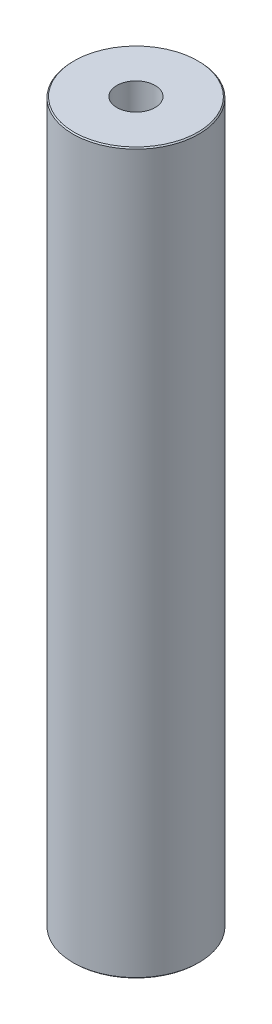
SolidWorks part; units mm, degrees
ref_plane "Front Plane" through (0, 0, 0) normal (0, 0, 1) x (1, 0, 0)
ref_plane "Top Plane" through (0, 0, 0) normal (0, 1, 0) x (1, 0, 0)
ref_plane "Right Plane" through (0, 0, 0) normal (1, 0, 0) x (0, 0, -1)
sketch "Sketch1" plane through (0, 0, 0) normal (0, 1, 0) x (1, 0, 0)
  circle A0 centre (0, 0) radius 52.5
  dimension "SHAFT_OD" = 105
extrude "Boss-Extrude1" add sketch "Sketch1" along normal blind 600
sketch "Sketch2" plane through (0, 0, 0) normal (0, 1, 0) x (1, 0, 0)
  circle A0 centre (0, 0) radius 15.9771
  dimension "BORE_D" = 31.9543
extrude "Cut-Extrude1" cut sketch "Sketch2" along normal through all
chamfer "Chamfer1" distance 0.9356 angle 45 2 edges at (0, 600, 52.5) (0, 0, 52.5)
